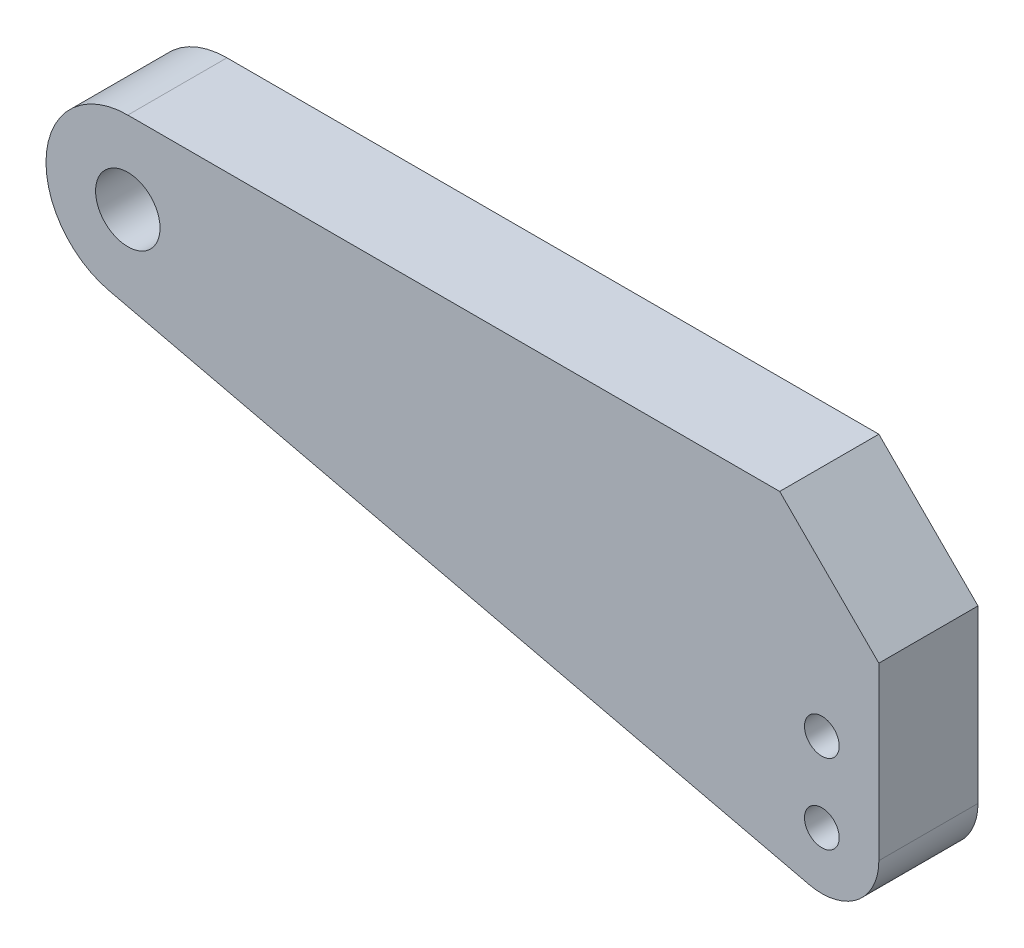
SolidWorks part; units mm, degrees
material "ABS PC"
ref_plane "Спереди" through (0, 0, 0) normal (0, 0, 1) x (1, 0, 0)
ref_plane "Сверху" through (0, 0, 0) normal (0, 1, 0) x (1, 0, 0)
ref_plane "Справа" through (0, 0, 0) normal (1, 0, 0) x (0, 0, -1)
sketch "Sketch1" plane through (0, 0, 0) normal (0, 0, 1) x (1, 0, 0)
  line L0 (65.75, 8.25) -> (0, 8.25)
  line L1 (75.75, -1.75) -> (65.75, 8.25)
  line L2 (-1.8854, -8.0317) -> (68.6859, -24.5978)
  line L6 (75.75, -19) -> (75.75, -1.75)
  circle A0 centre (0, 0) radius 3.25
  circle A1 centre (70, -11) radius 1.75
  circle A2 centre (70, -19) radius 1.75
  arc A3 (0, 8.25) -> (-1.8854, -8.0317) centre (0, 0) ccw
  arc A4 (68.6859, -24.5978) -> (75.75, -19) centre (70, -19) ccw
  point P7 (75.75, 8.25)
  dimension "D1" = 6.5
  dimension "D2" = 3.5
  dimension "D3" = 70
  dimension "D4" = 5
  dimension "D5" = 4
  dimension "D6" = 8
  dimension "D7" = 11
  dimension "D10" = 10
extrude "Boss-Extrude1" add sketch "Sketch1" along normal blind 10
